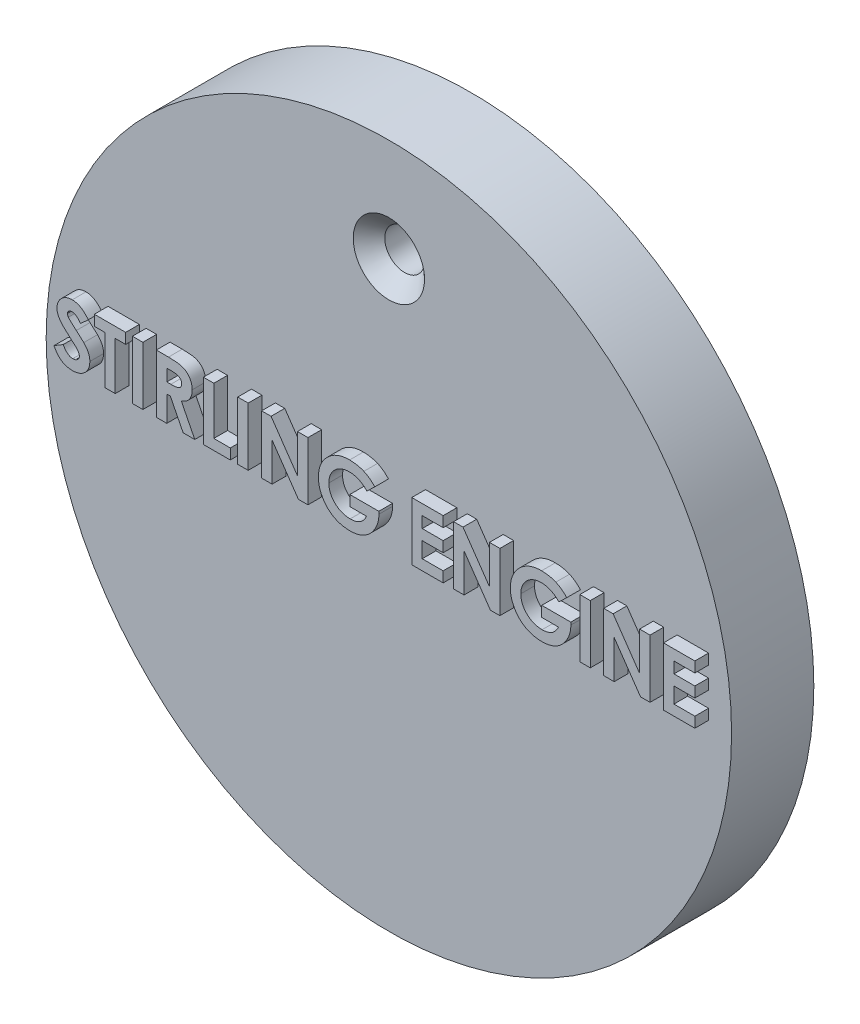
SolidWorks part; units mm, degrees
ref_plane "Front Plane" through (0, 0, 0) normal (0, 0, 1) x (1, 0, 0)
ref_plane "Top Plane" through (0, 0, 0) normal (0, 1, 0) x (1, 0, 0)
ref_plane "Right Plane" through (0, 0, 0) normal (1, 0, 0) x (0, 0, -1)
sketch "Sketch1" plane through (0, 0, 0) normal (0, 0, 1) x (1, 0, 0)
  circle A0 centre (0, 0) radius 50
  dimension "D1" = 100
extrude "Boss-Extrude2" add sketch "Sketch1" along normal blind 12
sketch "Sketch2" plane through (0, 0, 12) normal (0, 0, 1) x (1, 0, 0)
  line L0 (-50, 0) -> (50, 0) construction
  circle A0 centre (0, 0) radius 50 construction
  text T0 "STIRLING ENGINE" font "Century Gothic" height 8.5
extrude "Boss-Extrude3" add sketch "Sketch2" along normal blind 2
hole_wizard "CSK for M5 Flat Head Machine Screw1" positions "Sketch3" profile "Sketch4" countersink size "M5" standard "ANSI Metric" end condition through all
sketch "Sketch3" plane through (0, 0, 12) normal (0, 0, 1) x (1, 0, 0)
  point P0 (0, 35)
  dimension "D1" = 35
sketch "Sketch4" plane through (0, 35, 12) normal (1, 0, 0) x (0, -1, 0)
  line L0 (0, 0) -> (0, 12)
  line L1 (0, 12) -> (2.9, 12)
  line L2 (2.9, 12) -> (2.9, 2.3)
  line L3 (2.9, 2.3) -> (5.2, 0)
  line L5 (5.2, 0) -> (0, 0)
  line L6 (-2.9, 2.3) -> (-5.2, 0) construction
  line L11 (0, -6.35) -> (0, 107.95) construction
  dimension "Thru Hole Dia." = 5.8
  dimension "Thru Hole Depth" = 12
  dimension "Near C'Sink Dia." = 10.4
  dimension "Near C'Sink Angle" = 90
